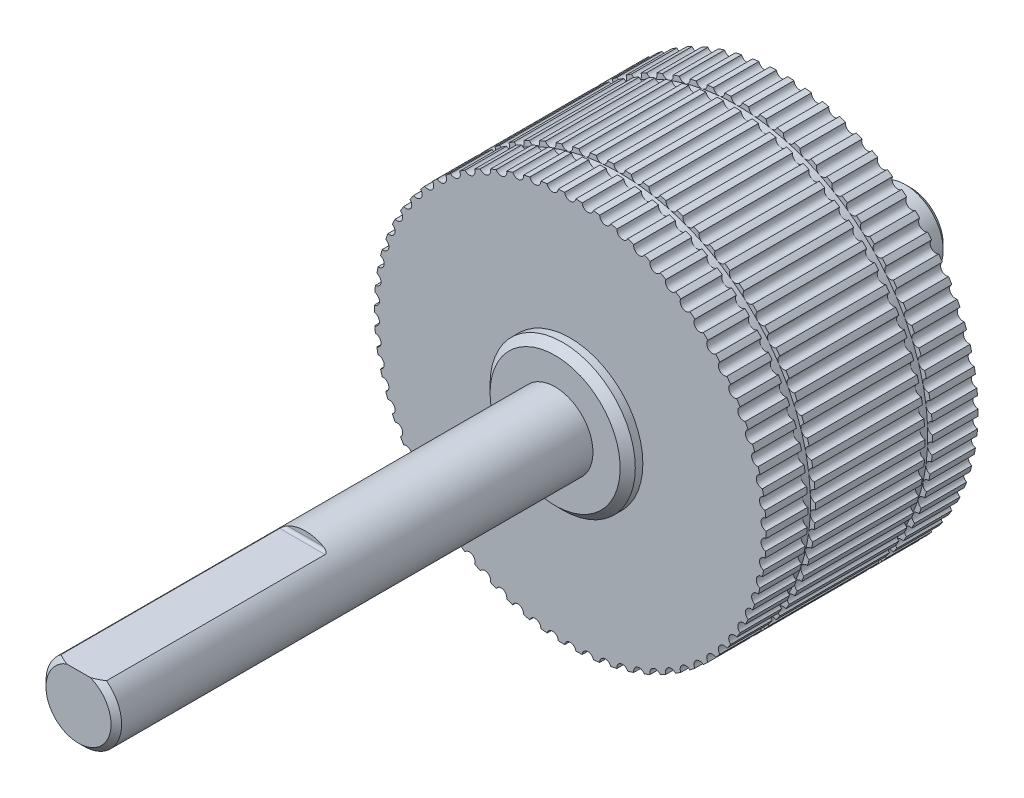
SolidWorks part; units mm, degrees
other "rotore"
other "albero"
ref_plane "Front Plane" through (0, 0, 0) normal (0, 0, 1) x (1, 0, 0)
ref_plane "Top Plane" through (0, 0, 0) normal (0, 1, 0) x (1, 0, 0)
ref_plane "Right Plane" through (0, 0, 0) normal (1, 0, 0) x (0, 0, -1)
sketch "Sketch2" plane through (0, 0, 0) normal (1, 0, 0) x (0, 0, -1)
  line L0 (0, 0) -> (7216.5414, 0) construction
  line L1 (-7, 4.8) -> (-7, 13)
  line L2 (-7, 2.5) -> (7, 2.5)
  line L3 (-7, 2.5) -> (-7, 13) construction
  line L4 (-7, 13) -> (7, 13)
  line L5 (7, 2.5) -> (7, 13) construction
  line L6 (-7, 2.5) -> (7, 13) construction
  line L7 (-7, 13) -> (7, 2.5) construction
  line L8 (-8, 4.8) -> (-7, 4.8)
  line L9 (-8, 4.8) -> (-8, 2.5)
  line L10 (-8, 2.5) -> (-7, 2.5)
  line L11 (-7, 4.8) -> (-7, 2.5) construction
  line L12 (-8, 4.8) -> (-7, 2.5) construction
  line L13 (-8, 2.5) -> (-7, 4.8) construction
  line L14 (7, 4.8) -> (8, 4.8)
  line L15 (7, 4.8) -> (7, 2.5) construction
  line L16 (7, 2.5) -> (8, 2.5)
  line L17 (8, 4.8) -> (8, 2.5)
  line L18 (7, 4.8) -> (8, 2.5) construction
  line L19 (7, 2.5) -> (8, 4.8) construction
  line L20 (7, 13) -> (7, 4.8)
  point P3 (0, 7.75)
  point P8 (7.5, 3.65)
  point P10 (-7.5, 3.65)
  dimension "D1" = 14
  dimension "D2" = 2.5
  dimension "D3" = 13
  dimension "D4" = 1
  dimension "D5" = 2.3
revolve "Revolve1" add sketch "Sketch2" angle 360 about L0
chamfer "Chamfer1" distance 0.5 angle 45 2 edges at (4.8, 0, -8) (4.8, 0, 8)
sketch "Sketch3" plane through (0, 0, 7) normal (0, 0, 1) x (1, 0, 0)
  circle A0 centre (0, 13) radius 0.375
  circle A1 centre (0, 0) radius 13 construction
  dimension "D1" = 0.75
extrude "Cut-Extrude1" cut sketch "Sketch3" against normal up to surface (14 mm away) up to face at (13, 0, -7)
pattern_circular "CirPattern1" count 70 over 360 about axis through (0, 0, 8) along (0, 0, 1) of "Cut-Extrude1"
sketch "Sketch4" plane through (0, 0, 7) normal (0, 0, 1) x (1, 0, 0)
  circle A0 centre (0, 0) radius 13
  circle A1 centre (0, 0) radius 12.625
  arc A2 (-11.6207, 5.8275) -> (-11.8015, 5.452) centre (0, 0) ccw construction
  arc A3 (-12.0963, 4.7624) -> (-11.8015, 5.452) centre (-11.9539, 5.1093) ccw construction
extrude "Cut-Extrude2" cut sketch "Sketch4" against normal mid plane 0.5 from offset 3 offset against normal yes
pattern_linear "LPattern1" count 2 spacing 7.75 along (0, 0, -1) of "Cut-Extrude2"
sketch "Sketch9" plane through (0, 0, 7) normal (0, 0, 1) x (1, 0, 0)
  circle A0 centre (0, 0) radius 13
  arc A1 (-12.0963, 4.7624) -> (-12.2427, 4.3722) centre (0, 0) ccw construction
  circle A2 centre (0, 0) radius 12.95
  dimension "D1" = 0.05
extrude "Cut-Extrude3" cut sketch "Sketch9" against normal up to surface (14 mm away) up to face at (0, 0, -7)
sketch "Sketch10" plane through (0, 0, 0) normal (0, 0, 1) x (1, 0, 0)
  circle A0 centre (0, 0) radius 2.5
  circle A1 centre (0, 0) radius 2.5 construction
  dimension "D1" = 5
extrude "Boss-Extrude1" add sketch "Sketch10" along normal blind 39.5 and the other way blind 15.5 separate body
chamfer "Chamfer2" distance 0.35 angle 45 2 edges at (2.5, 0, -15.5) (2.5, 0, 39.5)
sketch "Sketch11" plane through (0, 0, 39.5) normal (0, 0, 1) x (1, 0, 0)
  line L1 (-2.5, 2.5) -> (2.5, 2.5)
  line L2 (-2.5, 2.5) -> (-2.5, 2)
  line L3 (-2.5, 2) -> (2.5, 2)
  line L4 (2.5, 2.5) -> (2.5, 2)
  line L5 (-2.5, 2.5) -> (2.5, 2) construction
  line L6 (-2.5, 2) -> (2.5, 2.5) construction
  circle A1 centre (0, 0) radius 2.5 construction
  point P0 (0, 2.25)
  dimension "D1" = 0.5
extrude "Cut-Extrude4" cut sketch "Sketch11" against normal blind 15
fillet "Fillet1" radius 0.2 1 edges at (0, 2, 24.5)
